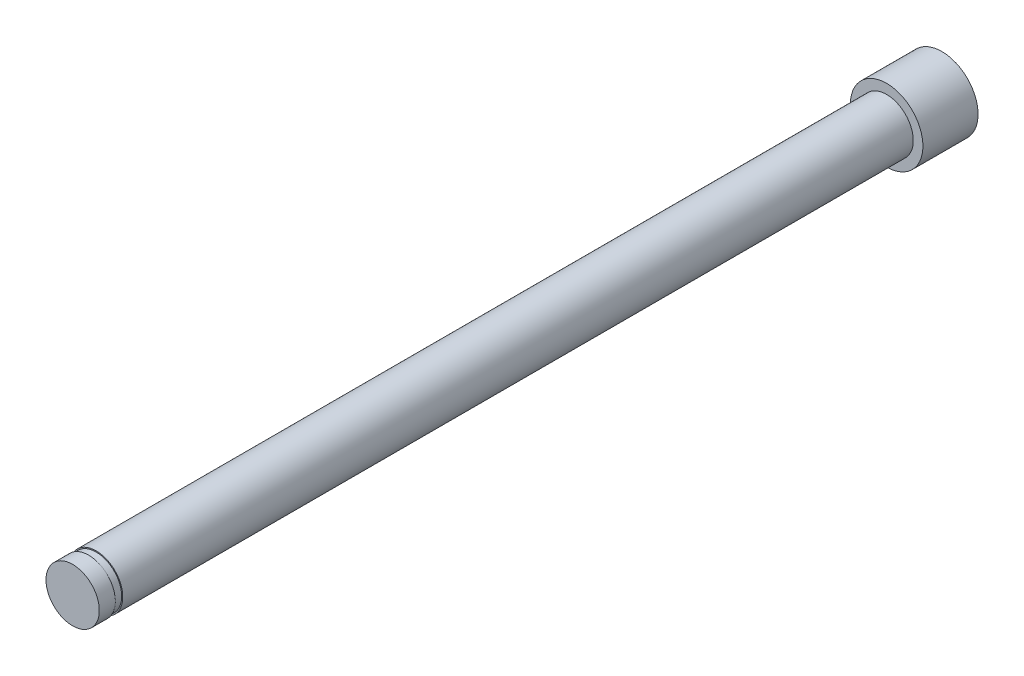
SolidWorks part; units mm, degrees
ref_plane "Front Plane" through (0, 0, 0) normal (0, 0, 1) x (1, 0, 0)
ref_plane "Top Plane" through (0, 0, 0) normal (0, 1, 0) x (1, 0, 0)
ref_plane "Right Plane" through (0, 0, 0) normal (1, 0, 0) x (0, 0, -1)
sketch "Sketch1" plane through (0, 0, 0) normal (0, 0, 1) x (1, 0, 0)
  circle A0 centre (0, 0) radius 2.5
  dimension "D1" = 5
extrude "Boss-Extrude1" add sketch "Sketch1" along normal mid plane 81.534
ref_axis "Axis1" through (0, 0, 40.767) along (0, 0, -1)
sketch "Sketch2" plane through (0, 0, 0) normal (1, 0, 0) x (0, 0, -1)
  line L0 (40.767, 2.5) -> (-40.767, 2.5) construction
  line L1 (-39.2646, 2.5) -> (-38.5646, 2.5)
  line L2 (-39.2646, 2.5) -> (-39.2646, 2.4)
  line L3 (-39.2646, 2.4) -> (-38.5646, 2.4)
  line L4 (-38.5646, 2.5) -> (-38.5646, 2.4)
  line L5 (-38.5646, -71.6242) -> (-38.5646, -65.2736) construction
  dimension "D1" = 0.1
  dimension "D2" = 0.7
revolve "Cut-Revolve1" cut sketch "Sketch2" angle 360 about axis through (0, 0, 40.767) along (0, 0, -1)
sketch "Sketch4" plane through (0, 0, -40.767) normal (0, 0, -1) x (-1, 0, 0)
  circle A0 centre (0, 0) radius 3.4022
extrude "Boss-Extrude2" add sketch "Sketch4" against normal up to surface (5.1753 mm away)
